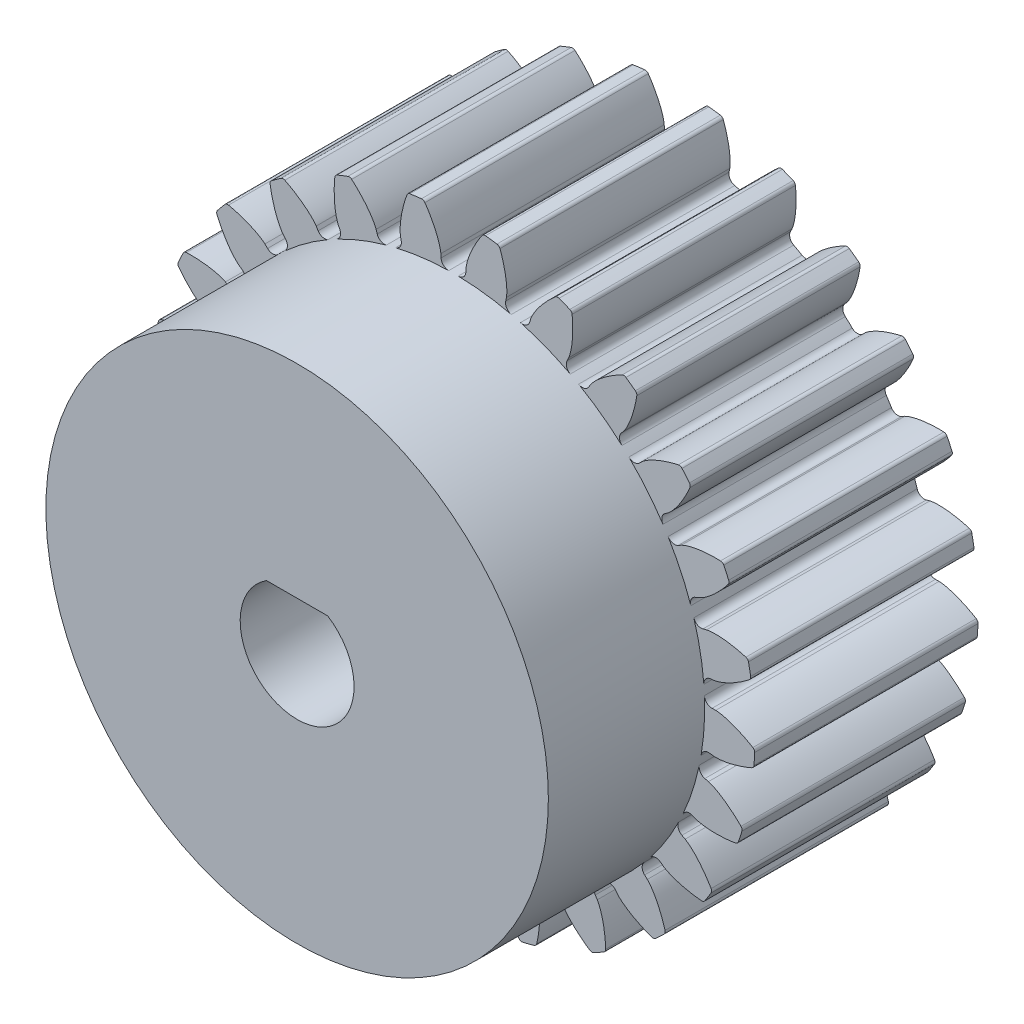
SolidWorks part; units mm, degrees
material "Alloy Steel"
ref_plane "Front" through (0, 0, 0) normal (0, 0, 1) x (1, 0, 0)
ref_plane "Top" through (0, 0, 0) normal (0, 1, 0) x (1, 0, 0)
ref_plane "Right" through (0, 0, 0) normal (1, 0, 0) x (0, 0, -1)
sketch "Sketch1" plane through (0, 0, 0) normal (0, 0, 1) x (1, 0, 0)
  circle A0 centre (0, 0) radius 13.5
  dimension "OutsideDiameter" = 27
extrude "Boss-Extrude1" add sketch "Sketch1" along normal blind 10
sketch "Sketch3" plane through (0, 0, 0) normal (0, 0, 1) x (1, 0, 0)
  line L0 (0, 0) -> (43.7181, 0) construction
  line L2 (0, 0) -> (-0.539, 11.2371) construction
  line L3 (0, 0) -> (0.539, 11.2371) construction
  line L4 (0.539, 11.2371) -> (0.5627, 11.7327) construction
  line L5 (0, 0) -> (0, 61.276) construction
  line L6 (-0.539, 11.2371) -> (-0.5627, 11.7327) construction
  circle A0 centre (0, 0) radius 13.5 construction
  circle A1 centre (0, 0) radius 12.5 construction
  circle A2 centre (0, 0) radius 11.7462 construction
  arc A3 (0.539, 11.2371) -> (-0.539, 11.2371) centre (0, 0) ccw construction
  arc A5 (1.3344, 13.4339) -> (-1.3344, 13.4339) centre (0, 0) ccw
  spline S0 degree 4 poles (-0.5627, 11.7327) (-0.5629, 11.7355) (-0.5635, 11.7432) (-0.565, 11.758) (-0.568, 11.7819) (-0.5727, 11.8124) (-0.5797, 11.8517) (-0.5892, 11.8979) (-0.601, 11.9485) (-0.6152, 12.0034) (-0.6307, 12.0579) (-0.6473, 12.1122) (-0.6648, 12.1662) (-0.6873, 12.2313) (-0.716, 12.3091) (-0.752, 12.3996) (-0.7958, 12.5017) (-0.8436, 12.6052) (-0.8931, 12.7065) (-0.9461, 12.8082) (-0.9995, 12.9061) (-1.0579, 13.0071) (-1.1133, 13.1) (-1.1787, 13.2033) (-1.2325, 13.2864) (-1.3069, 13.3951) (-1.3519, 13.459) (-1.4057, 13.5334) (-1.4302, 13.5663) (-1.4453, 13.5866) knots 0 0 0 0 0 0.005377 0.015084 0.028532 0.04661 0.064855 0.092111 0.119476 0.146842 0.174209 0.201575 0.228941 0.256307 0.307035 0.361767 0.4165 0.471232 0.525964 0.580697 0.635429 0.690161 0.744894 0.799626 0.854358 0.909091 0.954545 1 1 1 1 1 construction
  spline S1 degree 4 poles (-0.5627, 11.7327) (-0.5629, 11.7355) (-0.5635, 11.7432) (-0.565, 11.758) (-0.568, 11.7819) (-0.5727, 11.8124) (-0.5797, 11.8517) (-0.5892, 11.8979) (-0.601, 11.9485) (-0.6152, 12.0034) (-0.6307, 12.0579) (-0.6473, 12.1122) (-0.6648, 12.1662) (-0.6873, 12.2313) (-0.716, 12.3091) (-0.752, 12.3996) (-0.7958, 12.5017) (-0.8436, 12.6052) (-0.8931, 12.7065) (-0.9461, 12.8082) (-0.9995, 12.9061) (-1.0579, 13.0071) (-1.1133, 13.1) (-1.1787, 13.2033) (-1.2325, 13.2864) (-1.2907, 13.3715) (-1.3195, 13.4128) (-1.3344, 13.4339) knots 0 0 0 0 0 0.005377 0.015084 0.028532 0.04661 0.064855 0.092111 0.119476 0.146842 0.174209 0.201575 0.228941 0.256307 0.307035 0.361767 0.4165 0.471232 0.525964 0.580697 0.635429 0.690161 0.744894 0.799626 0.854358 0.909091 0.909091 0.909091 0.909091 0.909091
  spline S2 degree 4 poles (0.5627, 11.7327) (0.5629, 11.7355) (0.5635, 11.7432) (0.565, 11.758) (0.568, 11.7819) (0.5727, 11.8124) (0.5797, 11.8517) (0.5892, 11.8979) (0.601, 11.9485) (0.6152, 12.0034) (0.6307, 12.0579) (0.6473, 12.1122) (0.6648, 12.1662) (0.6873, 12.2313) (0.716, 12.3091) (0.752, 12.3996) (0.7958, 12.5017) (0.8436, 12.6052) (0.8931, 12.7065) (0.9461, 12.8082) (0.9995, 12.9061) (1.0579, 13.0071) (1.1133, 13.1) (1.1787, 13.2033) (1.2325, 13.2864) (1.3069, 13.3951) (1.3519, 13.459) (1.4057, 13.5334) (1.4302, 13.5663) (1.4453, 13.5866) knots 0 0 0 0 0 0.005377 0.015084 0.028532 0.04661 0.064855 0.092111 0.119476 0.146842 0.174209 0.201575 0.228941 0.256307 0.307035 0.361767 0.4165 0.471232 0.525964 0.580697 0.635429 0.690161 0.744894 0.799626 0.854358 0.909091 0.954545 1 1 1 1 1 construction
  spline S3 degree 4 poles (0.5627, 11.7327) (0.5629, 11.7355) (0.5635, 11.7432) (0.565, 11.758) (0.568, 11.7819) (0.5727, 11.8124) (0.5797, 11.8517) (0.5892, 11.8979) (0.601, 11.9485) (0.6152, 12.0034) (0.6307, 12.0579) (0.6473, 12.1122) (0.6648, 12.1662) (0.6873, 12.2313) (0.716, 12.3091) (0.752, 12.3996) (0.7958, 12.5017) (0.8436, 12.6052) (0.8931, 12.7065) (0.9461, 12.8082) (0.9995, 12.9061) (1.0579, 13.0071) (1.1133, 13.1) (1.1787, 13.2033) (1.2325, 13.2864) (1.2907, 13.3715) (1.3195, 13.4128) (1.3344, 13.4339) knots 0 0 0 0 0 0.005377 0.015084 0.028532 0.04661 0.064855 0.092111 0.119476 0.146842 0.174209 0.201575 0.228941 0.256307 0.307035 0.361767 0.4165 0.471232 0.525964 0.580697 0.635429 0.690161 0.744894 0.799626 0.854358 0.909091 0.909091 0.909091 0.909091 0.909091
  point P0 (0, 11.25)
  dimension "OutsideDiameter" = 27
  dimension "PitchCircle" = 25
  dimension "BaseCircle" = 23.4923
  dimension "DedendumCircle" = 22.5
sketch "DCLTBC" plane through (0, 0, 0) normal (0, 0, 1) x (1, 0, 0)
  line L0 (0, 0) -> (41.04, 0) construction
  line L1 (-0.539, 11.2371) -> (-0.5627, 11.7327) construction
  line L2 (0.539, 11.2371) -> (0.5627, 11.7327) construction
  line L3 (-0.539, 11.2371) -> (-0.5627, 11.7327)
  line L4 (0.539, 11.2371) -> (0.5627, 11.7327)
  line L5 (0, 0) -> (0, 104.9356) construction
  circle A0 centre (0, 0) radius 13.5
  circle A1 centre (0, 0) radius 12.5 construction
  circle A2 centre (0, 0) radius 11.7462 construction
  arc A3 (0.539, 11.2371) -> (-0.539, 11.2371) centre (0, 0) ccw construction
  arc A4 (0.539, 11.2371) -> (-0.539, 11.2371) centre (0, 0) ccw
  spline S0 degree 4 poles (-1995.7925, -124.0386) (-18.637, 9.6549) (-0.7482, 10.902) (-0.5144, 11.3546) (-0.568, 11.7819) (-0.5727, 11.8124) (-0.5797, 11.8517) (-0.5892, 11.8979) (-0.601, 11.9485) (-0.6152, 12.0034) (-0.6307, 12.0579) (-0.6473, 12.1122) (-0.6648, 12.1662) (-0.6873, 12.2313) (-0.716, 12.3091) (-0.752, 12.3996) (-0.7958, 12.5017) (-0.8436, 12.6052) (-0.8931, 12.7065) (-0.9461, 12.8082) (-0.9995, 12.9061) (-1.0579, 13.0071) (-1.1133, 13.1) (-1.1787, 13.2033) (-1.5156, 13.7241) (-2.9947, 15.6922) (22.2491, -20.3107) (-1154.5903, 1647.3833) knots -0.784355 -0.784355 -0.784355 -0.784355 -0.784355 0.005377 0.015084 0.028532 0.04661 0.064855 0.092111 0.119476 0.146842 0.174209 0.201575 0.228941 0.256307 0.307035 0.361767 0.4165 0.471232 0.525964 0.580697 0.635429 0.690161 0.744894 0.799626 0.854358 2.062408 2.062408 2.062408 2.062408 2.062408 only from (-0.5627, 11.7327) to (-1.3344, 13.4339) construction
  spline S1 degree 4 poles (1995.7925, -124.0386) (18.637, 9.6549) (0.7482, 10.902) (0.5144, 11.3546) (0.568, 11.7819) (0.5727, 11.8124) (0.5797, 11.8517) (0.5892, 11.8979) (0.601, 11.9485) (0.6152, 12.0034) (0.6307, 12.0579) (0.6473, 12.1122) (0.6648, 12.1662) (0.6873, 12.2313) (0.716, 12.3091) (0.752, 12.3996) (0.7958, 12.5017) (0.8436, 12.6052) (0.8931, 12.7065) (0.9461, 12.8082) (0.9995, 12.9061) (1.0579, 13.0071) (1.1133, 13.1) (1.1787, 13.2033) (1.5156, 13.7241) (2.9947, 15.6922) (-22.2491, -20.3107) (1154.5903, 1647.3833) knots -0.784355 -0.784355 -0.784355 -0.784355 -0.784355 0.005377 0.015084 0.028532 0.04661 0.064855 0.092111 0.119476 0.146842 0.174209 0.201575 0.228941 0.256307 0.307035 0.361767 0.4165 0.471232 0.525964 0.580697 0.635429 0.690161 0.744894 0.799626 0.854358 2.062408 2.062408 2.062408 2.062408 2.062408 only from (0.5627, 11.7327) to (1.3344, 13.4339) construction
  spline S2 degree 4 poles (-0.5627, 11.7327) (-0.5629, 11.7355) (-0.5635, 11.7432) (-0.565, 11.758) (-0.568, 11.7819) (-0.5727, 11.8124) (-0.5797, 11.8517) (-0.5892, 11.8979) (-0.601, 11.9485) (-0.6152, 12.0034) (-0.6307, 12.0579) (-0.6473, 12.1122) (-0.6648, 12.1662) (-0.6873, 12.2313) (-0.716, 12.3091) (-0.752, 12.3996) (-0.7958, 12.5017) (-0.8436, 12.6052) (-0.8931, 12.7065) (-0.9461, 12.8082) (-0.9995, 12.9061) (-1.0579, 13.0071) (-1.1133, 13.1) (-1.1787, 13.2033) (-1.2325, 13.2864) (-1.2907, 13.3715) (-1.3195, 13.4128) (-1.3344, 13.4339) knots 0 0 0 0 0 0.005377 0.015084 0.028532 0.04661 0.064855 0.092111 0.119476 0.146842 0.174209 0.201575 0.228941 0.256307 0.307035 0.361767 0.4165 0.471232 0.525964 0.580697 0.635429 0.690161 0.744894 0.799626 0.854358 0.909091 0.909091 0.909091 0.909091 0.909091
  spline S3 degree 4 poles (0.5627, 11.7327) (0.5629, 11.7355) (0.5635, 11.7432) (0.565, 11.758) (0.568, 11.7819) (0.5727, 11.8124) (0.5797, 11.8517) (0.5892, 11.8979) (0.601, 11.9485) (0.6152, 12.0034) (0.6307, 12.0579) (0.6473, 12.1122) (0.6648, 12.1662) (0.6873, 12.2313) (0.716, 12.3091) (0.752, 12.3996) (0.7958, 12.5017) (0.8436, 12.6052) (0.8931, 12.7065) (0.9461, 12.8082) (0.9995, 12.9061) (1.0579, 13.0071) (1.1133, 13.1) (1.1787, 13.2033) (1.2325, 13.2864) (1.2907, 13.3715) (1.3195, 13.4128) (1.3344, 13.4339) knots 0 0 0 0 0 0.005377 0.015084 0.028532 0.04661 0.064855 0.092111 0.119476 0.146842 0.174209 0.201575 0.228941 0.256307 0.307035 0.361767 0.4165 0.471232 0.525964 0.580697 0.635429 0.690161 0.744894 0.799626 0.854358 0.909091 0.909091 0.909091 0.909091 0.909091
  dimension "OutsideDiameter" = 27
  dimension "PitchCircle" = 25
  dimension "BaseCircle" = 23.4923
extrude "Cut-Extrude-DCLTBC" cut sketch "DCLTBC" along normal through all contours L4 S3 A0 S2 L3 A4 region at (0, 12.5544, 0)
fillet "Fillet-Tip-DCLTBC" radius 0.1678 2 edges at (1.3344, 13.4339, 5) (-1.3344, 13.4339, 5)
fillet "Fillet-Root-DCLTBC" radius 0.3355 2 edges at (-0.539, 11.2371, 5) (0.539, 11.2371, 5)
pattern_circular "CirPattern-DCLTBC" count 25 over 360 about axis through (0, 0, 10) along (0, 0, 1) of "Cut-Extrude-DCLTBC", "Fillet-Tip-DCLTBC", "Fillet-Root-DCLTBC"
sketch "DCGTBC" [suppressed] plane through (0, 0, 0) normal (0, 0, 1) x (1, 0, 0)
  line L0 (0, 0) -> (41.04, 0) construction
  line L1 (-118.2981, 10.3497) -> (0, 0) construction
  line L2 (0, 0) -> (118.2981, 10.3497) construction
  line L3 (0, 0) -> (-16.5124, 0)
  line L5 (0, 0) -> (0, 104.9356) construction
  circle A0 centre (0, 0) radius 130
  circle A1 centre (0, 0) radius 125 construction
  circle A2 centre (0, 0) radius 117.4616 construction
  arc A3 (1.9607, 118.7338) -> (-1.9607, 118.7338) centre (0, 0) ccw construction
  arc A11 (118.2981, 10.3497) -> (-118.2981, 10.3497) centre (0, 0) ccw
  spline S4 degree 4 poles (1000.8658, 71.4969) (19.2618, 112.6201) (2.2033, 114.4544) (1.8257, 116.1103) (1.9619, 117.792) (1.9844, 118.0069) (2.0191, 118.2845) (2.0674, 118.6114) (2.1283, 118.9703) (2.2028, 119.3605) (2.2847, 119.7495) (2.3732, 120.1373) (2.4676, 120.5233) (2.5893, 120.9905) (2.7454, 121.5503) (2.9429, 122.2037) (3.1845, 122.9439) (3.4495, 123.6971) (3.7258, 124.4373) (4.0228, 125.184) (4.3228, 125.9056) (4.6527, 126.6539) (4.9665, 127.3439) (5.3384, 128.1155) (6.4568, 130.3899) (9.6326, 136.112) (-11.5818, 95.9351) (478.0107, 1011.5506) knots -0.41793 -0.41793 -0.41793 -0.41793 -0.41793 0.005377 0.015084 0.028532 0.04661 0.064855 0.092111 0.119476 0.146842 0.174209 0.201575 0.228941 0.256307 0.307035 0.361767 0.4165 0.471232 0.525964 0.580697 0.635429 0.690161 0.744894 0.799626 0.854358 1.490341 1.490341 1.490341 1.490341 1.490341 only from (1.9394, 117.4456) to (6.2272, 129.8508) construction
  spline S5 degree 4 poles (-1000.8658, 71.4969) (-19.2618, 112.6201) (-2.2033, 114.4544) (-1.8257, 116.1103) (-1.9619, 117.792) (-1.9844, 118.0069) (-2.0191, 118.2845) (-2.0674, 118.6114) (-2.1283, 118.9703) (-2.2028, 119.3605) (-2.2847, 119.7495) (-2.3732, 120.1373) (-2.4676, 120.5233) (-2.5893, 120.9905) (-2.7454, 121.5503) (-2.9429, 122.2037) (-3.1845, 122.9439) (-3.4495, 123.6971) (-3.7258, 124.4373) (-4.0228, 125.184) (-4.3228, 125.9056) (-4.6527, 126.6539) (-4.9665, 127.3439) (-5.3384, 128.1155) (-6.4568, 130.3899) (-9.6326, 136.112) (11.5818, 95.9351) (-478.0107, 1011.5506) knots -0.41793 -0.41793 -0.41793 -0.41793 -0.41793 0.005377 0.015084 0.028532 0.04661 0.064855 0.092111 0.119476 0.146842 0.174209 0.201575 0.228941 0.256307 0.307035 0.361767 0.4165 0.471232 0.525964 0.580697 0.635429 0.690161 0.744894 0.799626 0.854358 1.490341 1.490341 1.490341 1.490341 1.490341 only from (-1.9394, 117.4456) to (-6.2272, 129.8508) construction
  spline S6 degree 4 poles (1.9394, 117.4456) (1.9399, 117.4651) (1.942, 117.5198) (1.9483, 117.6233) (1.9619, 117.792) (1.9844, 118.0069) (2.0191, 118.2845) (2.0674, 118.6114) (2.1283, 118.9703) (2.2028, 119.3605) (2.2847, 119.7495) (2.3732, 120.1373) (2.4676, 120.5233) (2.5893, 120.9905) (2.7454, 121.5503) (2.9429, 122.2037) (3.1845, 122.9439) (3.4495, 123.6971) (3.7258, 124.4373) (4.0228, 125.184) (4.3228, 125.9056) (4.6527, 126.6539) (4.9665, 127.3439) (5.3384, 128.1155) (5.6444, 128.7378) (5.9774, 129.3793) (6.142, 129.6914) (6.2272, 129.8508) knots 0 0 0 0 0 0.005377 0.015084 0.028532 0.04661 0.064855 0.092111 0.119476 0.146842 0.174209 0.201575 0.228941 0.256307 0.307035 0.361767 0.4165 0.471232 0.525964 0.580697 0.635429 0.690161 0.744894 0.799626 0.854358 0.909091 0.909091 0.909091 0.909091 0.909091
  spline S7 degree 4 poles (-1.9394, 117.4456) (-1.9399, 117.4651) (-1.942, 117.5198) (-1.9483, 117.6233) (-1.9619, 117.792) (-1.9844, 118.0069) (-2.0191, 118.2845) (-2.0674, 118.6114) (-2.1283, 118.9703) (-2.2028, 119.3605) (-2.2847, 119.7495) (-2.3732, 120.1373) (-2.4676, 120.5233) (-2.5893, 120.9905) (-2.7454, 121.5503) (-2.9429, 122.2037) (-3.1845, 122.9439) (-3.4495, 123.6971) (-3.7258, 124.4373) (-4.0228, 125.184) (-4.3228, 125.9056) (-4.6527, 126.6539) (-4.9665, 127.3439) (-5.3384, 128.1155) (-5.6444, 128.7378) (-5.9774, 129.3793) (-6.142, 129.6914) (-6.2272, 129.8508) knots 0 0 0 0 0 0.005377 0.015084 0.028532 0.04661 0.064855 0.092111 0.119476 0.146842 0.174209 0.201575 0.228941 0.256307 0.307035 0.361767 0.4165 0.471232 0.525964 0.580697 0.635429 0.690161 0.744894 0.799626 0.854358 0.909091 0.909091 0.909091 0.909091 0.909091
  dimension "D1" = 5
  dimension "D2" = 5
  dimension "OutsideDiameter" = 27
  dimension "PitchCircle" = 25
  dimension "BaseCircle" = 23.4923
extrude "Cut-Extrude-DCGTBC" [suppressed] cut sketch "DCGTBC" along normal through all
fillet "Fillet-Tip-DCGTBC" [suppressed] radius 0.1678
pattern_circular "CirPattern-DCGTBC" [suppressed] count 25 over 360 of bodies 112
sketch "Sketch5" plane through (0, 0, 10) normal (0, 0, 1) x (1, 0, 0)
  circle A0 centre (0, 0) radius 11.25
  arc A1 (0.2133, 11.248) -> (-0.2133, 11.248) centre (0, 0) ccw construction
extrude "Boss-Extrude2" add sketch "Sketch5" along normal blind 7
sketch "Sketch6" plane through (0, 0, 0) normal (0, 0, -1) x (-1, 0, 0)
  line L0 (-1.3711, 2.15) -> (1.3711, 2.15)
  arc A0 (-1.3711, 2.15) -> (1.3711, 2.15) centre (0, 0) ccw
  dimension "D1" = 5.1
  dimension "D2" = 2.15
extrude "Cut-Extrude1" cut sketch "Sketch6" against normal through all both and the other way through all
sketch "Sketch7" plane through (0, 0, 0) normal (0, 0, -1) x (-1, 0, 0)
  circle A0 centre (0, 0) radius 12.5
  dimension "D1" = 25
sketch "Sketch8" plane through (0, 0, 10) normal (0, 0, 1) x (1, 0, 0)
  circle A0 centre (0, 0) radius 12.5
  dimension "D1" = 25
equation "\"DiametralPitch\"= 25.4 / 1 'Diametral Pitch"
equation "\"NumTeeth\"= 25 'Number of Teeth"
equation "\"PressureAngle\"= 20deg'Pressure Angle"
equation "\"Addendum\"= 1 / \"DiametralPitch\"'Addendum"
equation "\"Dedendum\"= 1.25 / \"DiametralPitch\"'Dedendum"
equation "\"WorkingDepth\"= 2 / \"DiametralPitch\"'Working Depth - here for REF (Not used in building model)"
equation "\"WholeDepth\"= 2.25 / \"DiametralPitch\"'Whole Depth - here for REF (Not used in building model)"
equation "\"Clearance\"= .25 / \"DiametralPitch\"'Clearance"
equation "\"CircularPitch\"= pi / \"DiametralPitch\"'Circular Pitch - here for REF (Not used in building model)"
equation "\"PitchCircle\"= \"NumTeeth\" / \"DiametralPitch\"'Pitch Circle - or - Pitch Diameter"
equation "\"OutsideDiameter\"= ( \"NumTeeth\" + 2 ) / \"DiametralPitch\"'Outside Diameter"
equation "\"Fillet_Root\"= \"Clearance\" * cos ( \"PressureAngle\" ) * tan ( ( 90 + \"PressureAngle\" ) / 2 ) 'Fillet Root"
equation "\"AddendumCircle\"= \"PitchCircle\" + ( 2 * \"Addendum\" )'Addendum Circle - or - Addendum Diameter"
equation "\"DedendumCircle\"= \"PitchCircle\" - ( 2 * \"Dedendum\" )'Dedendum Circle - or - Dedendum Diameter"
equation "\"BaseCircle\"= \"PitchCircle\" * cos ( \"PressureAngle\" )'Base Circle - Base Diameter"
equation "\"PitchAngle\"= 360deg / \"NumTeeth\"'Pitch Angle"
equation "\"Alpha\"= sqr ( \"PitchCircle\" ^ 2 - \"BaseCircle\" ^ 2 ) / \"BaseCircle\" * 180 / PI - \"PressureAngle\"'Alpha - Used for Calculating Beta"
equation "\"Beta\"= ( \"PitchAngle\" / 4 - ( \"Alpha\" - 90 ) )'Beta - Used in definition of the parameters for the parametric equation driven curve"
equation "\"Gamma\"= ( \"PitchAngle\" / 4 - ( \"Alpha\" + 90 ) )'Gamma - Used in definition of the parameters for the parametric equation driven curve"
equation "\"Phi\"= sqr ( ( \"AddendumCircle\" / 2 ) ^ 2 - ( \"BaseCircle\" / 2 ) ^ 2 ) / ( \"BaseCircle\" / 2 )'Phi - Used in definition of the parameters for the parametric equation driven curve"
equation "\"DCGTBC\"= iif ( \"DedendumCircle\" > \"BaseCircle\" , \"unsuppressed\" , \"suppressed\" )'if Dedendum Circle IS GREATER THAN BaseCircle THEN UnsuppressORSuppress FEATURE"
equation "\"DCLTBC\"= iif ( \"DedendumCircle\" - .002 > \"BaseCircle\" , \"suppressed\" , \"unsuppressed\" )'if Dedendum Circle - .002 IS GREATER THAN BaseCircle THEN SuppressORUnsuppress FEATURE"
equation "\"Cut-Extrude-DCGTBC\"= iif ( \"DedendumCircle\" > \"BaseCircle\" , \"unsuppressed\" , \"suppressed\" )'if Dedendum Circle IS GREATER THAN BaseCircle THEN UnsuppressORSuppress FEATURE"
equation "\"Cut-Extrude-DCLTBC\"= iif ( \"DedendumCircle\" - .002 > \"BaseCircle\" , \"suppressed\" , \"unsuppressed\" )'if Dedendum Circle - .002 IS GREATER THAN BaseCircle THEN SuppressORUnsuppress FEATURE"
equation "\"CirPattern-DCGTBC\"= iif ( \"DedendumCircle\" > \"BaseCircle\" , \"unsuppressed\" , \"suppressed\" )'if Dedendum Circle IS GREATER THAN BaseCircle THEN UnsuppressORSuppress FEATURE"
equation "\"CirPattern-DCLTBC\"= iif ( \"DedendumCircle\" - .002 > \"BaseCircle\" , \"suppressed\" , \"unsuppressed\" )'if Dedendum Circle - .002 IS GREATER THAN BaseCircle THEN SuppressORUnsuppress FEATURE"
equation "\"Fillet-Tip-DCGTBC\"= iif ( \"DedendumCircle\" > \"BaseCircle\" , \"unsuppressed\" , \"suppressed\" )'if Dedendum Circle IS GREATER THAN BaseCircle THEN UnsuppressORSuppress FEATURE"
equation "\"Fillet-Tip-DCLTBC\"= iif ( \"DedendumCircle\" - .002 > \"BaseCircle\" , \"suppressed\" , \"unsuppressed\" )'if Dedendum Circle - .002 IS GREATER THAN BaseCircle THEN SuppressORUnsuppress FEATURE"
equation "\"Fillet-Root-DCLTBC\"= iif ( \"DedendumCircle\" - .002 > \"BaseCircle\" , \"suppressed\" , \"unsuppressed\" )'if Dedendum Circle - .002 IS GREATER THAN BaseCircle THEN SuppressORUnsuppress FEATURE"
equation "\"D1@CirPattern-DCGTBC\"= \"NumTeeth\"'Number of Teeth"
equation "\"D1@CirPattern-DCLTBC\"= \"NumTeeth\"'Number of Teeth"
equation "\"D1@Fillet-Tip-DCGTBC\"= \"Fillet_Root\" / 2 'Tip Rad For Large No of Teeth"
equation "\"D1@Fillet-Tip-DCLTBC\"=\"Fillet_Root\" / 2'Tip Rad For Small No of Teeth"
equation "\"D1@Fillet-Root-DCLTBC\"= \"Fillet_Root\"'Fillet Root"
equation "\"D2@Sketch6\"=\"D1@Sketch6\"/2-0.4mm"
